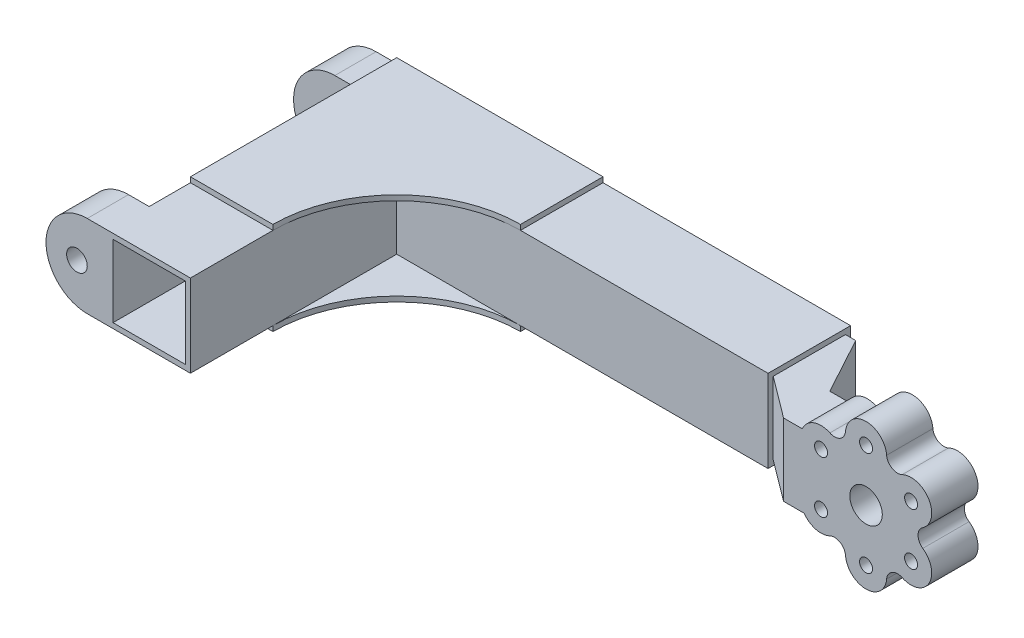
SolidWorks part; units mm, degrees
other "Markup1"
sketch "Sketch20" plane through (396.0128, 71.1753, 177.8) normal (0.1374, 0.3827, 0.9136) x (0.8813, 0.3738, -0.2891)
material "6061-T6 (SS)"
ref_plane "Front Plane" through (0, 0, 0) normal (0, 0, 1) x (1, 0, 0)
ref_plane "Top Plane" through (0, 0, 0) normal (0, 1, 0) x (1, 0, 0)
ref_plane "Right Plane" through (0, 0, 0) normal (1, 0, 0) x (0, 0, -1)
sketch "Sketch3" plane through (0, 0, 0) normal (0, 0, 1) x (1, 0, 0)
  line L0 (3.175, 47.625) -> (47.625, 47.625)
  line L1 (0, 0) -> (50.8, 0)
  line L2 (0, 0) -> (0, 50.8)
  line L3 (0, 50.8) -> (50.8, 50.8)
  line L4 (50.8, 0) -> (50.8, 50.8)
  line L5 (47.625, 3.175) -> (47.625, 47.625)
  line L6 (3.175, 3.175) -> (47.625, 3.175)
  line L7 (3.175, 3.175) -> (3.175, 47.625)
  dimension "D1" = 50.8
  dimension "D2" = 50.8
  dimension "D3" = 3.175
extrude "Boss-Extrude1" add sketch "Sketch3" along normal blind 177.8
sketch "Sketch4" plane through (0, 0, 0) normal (-1, 0, 0) x (0, 0, 1)
  line L0 (177.8, 0) -> (0, 0) construction
  line L1 (0, 50.8) -> (25.4, 50.8)
  line L2 (0, 50.8) -> (0, 0)
  line L3 (0, 0) -> (25.4, 0)
  line L4 (25.4, 50.8) -> (25.4, 0)
  line L6 (177.8, 50.8) -> (152.4, 50.8)
  line L7 (177.8, 50.8) -> (177.8, 0)
  line L8 (177.8, 0) -> (152.4, 0)
  line L9 (152.4, 50.8) -> (152.4, 0)
  dimension "D1" = 25.4
  dimension "D2" = 25.4
extrude "Boss-Extrude2" add sketch "Sketch4" along normal blind 38.1
fillet "Fillet1" radius 25.4 4 edges at (-38.1, 50.8, 12.7) (-38.1, 0, 12.7) (-38.1, 0, 165.1) (-38.1, 50.8, 165.1)
sketch "Sketch7" plane through (0, 0, 177.8) normal (0, 0, 1) x (1, 0, 0)
  circle A0 centre (-19.05, 25.4) radius 6.35
  point P5 (-38.1, 25.4)
  dimension "D2" = 12.7
  dimension "D1" = 19.05
extrude "Cut-Extrude1" cut sketch "Sketch7" against normal through all
sketch "Sketch8" plane through (50.8, 0, 0) normal (1, 0, 0) x (0, 0, -1)
  line L0 (-177.8, 50.8) -> (0, 50.8) construction
  line L1 (0, 0) -> (-50.8, 0)
  line L2 (0, 0) -> (0, 50.8)
  line L3 (0, 50.8) -> (-50.8, 50.8)
  line L4 (-50.8, 0) -> (-50.8, 50.8)
  line L6 (-3.175, 3.175) -> (-47.625, 3.175)
  line L7 (-3.175, 3.175) -> (-3.175, 47.625)
  line L8 (-3.175, 47.625) -> (-47.625, 47.625)
  line L9 (-47.625, 3.175) -> (-47.625, 47.625)
  dimension "D1" = 50.8
  dimension "D2" = 3.175
  dimension "D3" = 3.175
  dimension "D4" = 3.175
  dimension "D5" = 3.175
extrude "Boss-Extrude3" add sketch "Sketch8" along normal blind 228.6
sketch "Sketch9" plane through (0, 50.8, 0) normal (0, 1, 0) x (1, 0, 0)
  line L1 (279.4, -50.8) -> (50.8, -50.8) construction
  line L2 (50.8, -177.8) -> (50.8, -50.8) construction
  line L4 (0, -152.4) -> (0, -25.4) construction
  line L5 (0, -127) -> (0, 0)
  line L6 (0, 0) -> (127, 0)
  line L7 (279.4, 0) -> (-12.7, 0) construction
  line L8 (127, 0) -> (127, -50.8)
  line L10 (50.8, -127) -> (0, -127)
  arc A0 (127, -50.8) -> (50.8, -127) centre (127, -127) ccw
  dimension "D1" = 127
extrude "Boss-Extrude4" add sketch "Sketch9" along normal blind 3.175
sketch "Sketch10" plane through (0, 0, 0) normal (0, -1, 0) x (1, 0, 0)
  line L0 (0, 127) -> (0, 0)
  line L1 (0, 152.4) -> (0, 25.4) construction
  line L2 (0, 0) -> (127, 0)
  line L3 (-12.7, 0) -> (279.4, 0) construction
  line L4 (127, 0) -> (127, 50.8)
  line L5 (279.4, 50.8) -> (50.8, 50.8) construction
  line L7 (50.8, 177.8) -> (50.8, 50.8) construction
  line L8 (50.8, 127) -> (0, 127)
  arc A0 (50.8, 127) -> (127, 50.8) centre (127, 127) ccw
  dimension "D2" = 127
extrude "Boss-Extrude5" add sketch "Sketch10" along normal blind 3.175
sketch "Sketch11" plane through (279.4, 0, 0) normal (1, 0, 0) x (0, 0, -1)
  line L1 (-47.625, 47.625) -> (-3.175, 47.625)
  line L2 (-47.625, 47.625) -> (-47.625, 3.175)
  line L3 (-47.625, 3.175) -> (-3.175, 3.175)
  line L4 (-3.175, 47.625) -> (-3.175, 3.175)
extrude "Boss-Extrude6" add sketch "Sketch11" against normal blind 25.4
sketch "Sketch12" plane through (279.4, 0, 0) normal (1, 0, 0) x (0, 0, -1)
  line L0 (0, 50.8) -> (-50.8, 50.8) construction
  line L1 (-47.625, 50.8) -> (-3.175, 50.8)
  line L2 (-47.625, 50.8) -> (-47.625, 0)
  line L3 (-47.625, 0) -> (-3.175, 0)
  line L4 (-3.175, 50.8) -> (-3.175, 0)
  line L5 (-50.8, 0) -> (0, 0) construction
  line L6 (-50.8, 50.8) -> (-50.8, 0) construction
  line L7 (0, 0) -> (0, 50.8) construction
  dimension "D1" = 3.175
  dimension "D2" = 3.175
sketch "Sketch13" plane through (0, 0, 0) normal (0, 1, 0) x (1, 0, 0)
  line L0 (279.4, -47.625) -> (279.4, -3.175) construction
  line L1 (279.4, -47.625) -> (279.4, -3.175)
  line L2 (279.4, -3.175) -> (406.4, -3.175)
  line L3 (406.4, -3.175) -> (406.4, -66.675)
  line L4 (406.4, -66.675) -> (279.4, -66.675)
  line L5 (279.4, -47.625) -> (279.4, -66.675)
  line L8 (285.75, -3.175) -> (304.8, -38.175)
  line L9 (304.8, -38.175) -> (406.4, -38.175)
  line L10 (279.4, -47.625) -> (304.8, -66.675)
  dimension "D1" = 101.6
  dimension "D2" = 63.5
  dimension "D3" = 6.35
  dimension "D4" = 28.5
  dimension "D5" = 25.4
  dimension "D6" = 25.4
extrude "Boss-Extrude8" add sketch "Sketch13" along normal blind 76.2 and the other way blind 25.4 contours L1 L10 L4 L3 L9 L8 L2 region at (338.5706, 0, 47.9483)
sketch "Sketch14" plane through (0, 0, 66.675) normal (0, 0, 1) x (1, 0, 0)
  line L1 (406.4, -25.4) -> (304.8, -25.4)
  line L2 (406.4, -25.4) -> (406.4, 78.3505)
  line L3 (406.4, 78.3505) -> (304.8, 78.3505)
  line L4 (304.8, -25.4) -> (304.8, 78.3505)
  line L5 (279.4, 50.8) -> (279.4, 0) construction
  line L6 (279.4, 50.8) -> (279.4, 0)
  line L7 (279.4, 47.625) -> (316.2781, 47.625)
  line L8 (304.8, 26.4753) -> (406.4, 26.4753)
  line L9 (355.6, 78.3505) -> (355.6, -25.4)
  line L10 (279.4, 41.4) -> (279.4, 9.4)
  line L11 (279.4, 50.8) -> (127, 50.8) construction
  line L12 (279.4, 3.175) -> (317.4951, 3.175)
  line L13 (279.4, 50.8) -> (279.4, 78.3505)
  line L14 (279.4, 78.3505) -> (304.8, 78.3505)
  line L15 (279.4, 0) -> (279.4, -25.4)
  line L16 (279.4, -25.4) -> (304.8, -25.4)
  circle A0 centre (355.6, 26.4753) radius 32
  circle A1 centre (355.6, 58.4753) radius 4
  circle A2 centre (383.3128, 42.4753) radius 4
  circle A3 centre (383.3128, 10.4753) radius 4
  circle A4 centre (355.6, -5.5247) radius 4
  circle A5 centre (327.8872, 10.4753) radius 4
  circle A6 centre (327.8872, 42.4753) radius 4
  circle A7 centre (327.8872, 42.4753) radius 12.7
  circle A8 centre (355.6, 58.4753) radius 12.7
  circle A9 centre (383.3128, 42.4753) radius 12.7
  circle A10 centre (383.3128, 10.4753) radius 12.7
  circle A11 centre (355.6, -5.5247) radius 12.7
  circle A13 centre (327.8872, 10.4753) radius 12.7
  circle A14 centre (327.8872, 10.4753) radius 12.7 [skipped]
  arc A15 (320.6885, 32.0125) -> (320.6885, 20.938) centre (316.8787, 26.4753) cw
  arc A16 (368.2603, 59.4781) -> (377.8512, 53.9409) centre (374.9606, 60.0089) ccw
  arc A17 (390.5115, 32.0125) -> (390.5115, 20.938) centre (394.3213, 26.4753) ccw
  arc A18 (377.8512, -0.9904) -> (368.2603, -6.5276) centre (374.9606, -7.0584) ccw
  arc A19 (342.9397, -6.5276) -> (333.3488, -0.9904) centre (336.2394, -7.0584) ccw
  arc A20 (320.6885, 20.938) -> (320.6885, 32.0125) centre (316.8787, 26.4753) ccw
  circle A21 centre (355.6, 26.4753) radius 10
  arc A22 (333.3488, 53.9409) -> (342.9397, 59.4781) centre (336.2394, 60.0089) ccw
  point P24 (355.6, 26.4753)
  point P38 (355.6, 26.4753)
  point P44 (355.6, 26.4753)
  point P73 (355.6, 26.4753)
  point P75 (342.9, 25.4)
  line M46 (406.4, -25.4) -> (406.4, 76.2)
  line M47 (406.4, 76.2) -> (304.8, 76.2)
  line M49 (304.8, -25.4) -> (406.4, -25.4)
  line M53 (304.8, 76.2) -> (304.8, -25.4)
  dimension "D2" = 64
  dimension "D3" = 8
  dimension "D5" = 25.4
  dimension "D7" = 25.4
  dimension "D11" = 20
  dimension "D9" = 3.175
  dimension "D10" = 3.175
  dimension "D12" = 25.4
  dimension "D8" = 50.8
  dimension "D4" = 6
  dimension "D6" = 6
  dimension "D13" = 6
sketch "Sketch16" plane through (0, 0, 66.675) normal (0, 0, 1) x (1, 0, 0)
  line L1 (349.1781, 64.5727) -> (413.4709, 64.5727)
  line L2 (349.1781, 64.5727) -> (349.1781, -12.8346)
  line L3 (349.1781, -12.8346) -> (413.4709, -12.8346)
  line L4 (413.4709, 64.5727) -> (413.4709, -12.8346)
extrude "Cut-Extrude4" cut sketch "Sketch14" against normal through all contours L14 L13 L6 L7 M53 | A8 L9 L3 L7 A7 M53 | L8 L2 L9 A8 A9 M47 | A11 L9 L1 L8 A10 M46 | A13 L12 L4 L9 A11 M49 | L15 L16 L4 L12 L6 | A5 | A6 | A1 | A2 | A3 | A4 | A21 region at (388.3985, -6.9308, 66.675) region at (325.8799, -13.3165, 66.675) region at (389.0196, 58.4212, 66.675) region at (292.1, -11.1125, 66.675) region at (325.0358, 64.644, 66.675) region at (292.1, 62.9878, 66.675)
